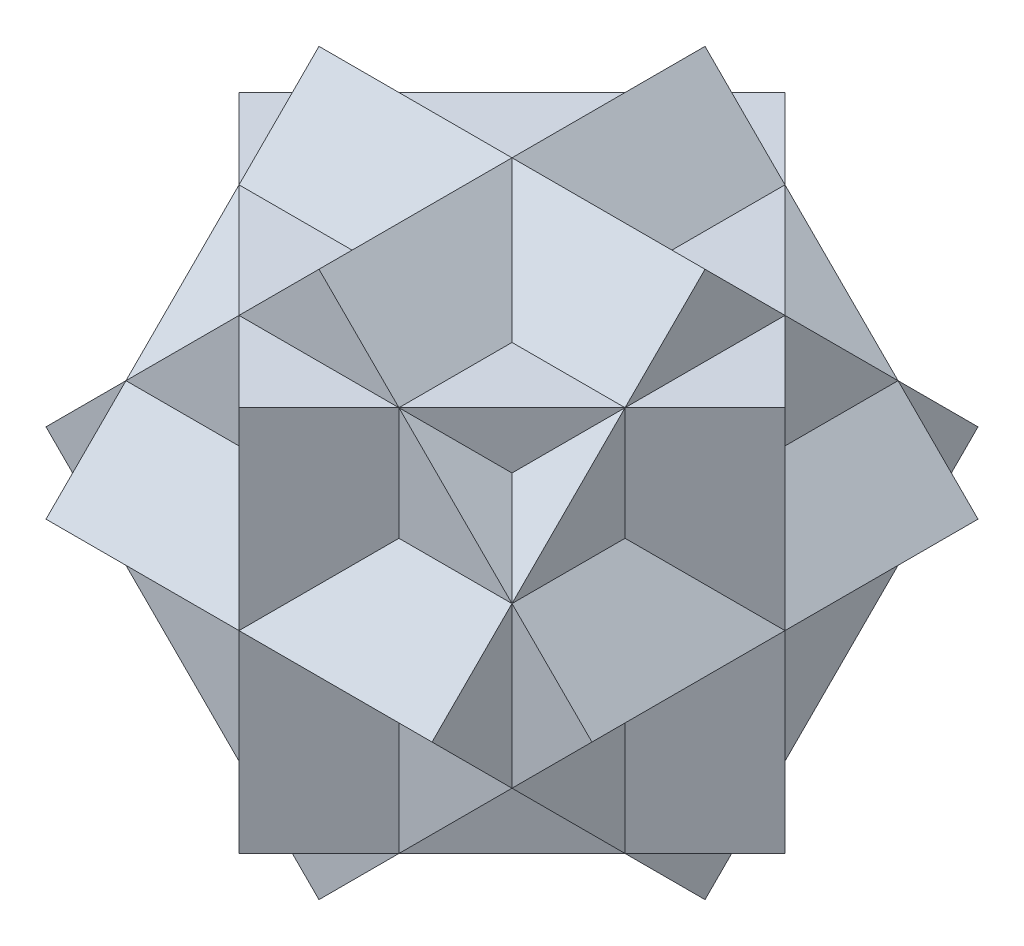
SolidWorks part; units mm, degrees
ref_plane "Front Plane" through (0, 0, 0) normal (0, 0, 1) x (1, 0, 0)
ref_plane "Top Plane" through (0, 0, 0) normal (0, 1, 0) x (1, 0, 0)
ref_plane "Right Plane" through (0, 0, 0) normal (1, 0, 0) x (0, 0, -1)
sketch "Sketch3" plane through (0, 0, 0) normal (0, 0, 1) x (1, 0, 0)
  line L0 (-160.803, 0) -> (0, 160.803)
  line L1 (-160.803, 0) -> (0, -160.803)
  line L2 (0, 160.803) -> (160.803, 0)
  line L3 (0, -160.803) -> (160.803, 0)
  line L4 (-160.803, 0) -> (160.803, 0) construction
  line L5 (0, 160.803) -> (0, -160.803) construction
  point P1 (0, 0)
  dimension "D1" = 227.4098
sketch "Sketch4" plane through (0, 0, 0) normal (0, 1, 0) x (1, 0, 0)
  line L0 (-160.803, 0) -> (0, 160.803)
  line L1 (-160.803, 0) -> (0, -160.803)
  line L2 (0, 160.803) -> (160.803, 0)
  line L3 (0, -160.803) -> (160.803, 0)
  line L4 (-160.803, 0) -> (160.803, 0) construction
  line L5 (0, 160.803) -> (0, -160.803) construction
  point P1 (0, 0)
sketch "Sketch5" plane through (0, 0, 0) normal (1, 0, 0) x (0, 0, -1)
  line L0 (-160.803, 0) -> (0, 160.803)
  line L1 (-160.803, 0) -> (0, -160.803)
  line L2 (0, 160.803) -> (160.803, 0)
  line L3 (0, -160.803) -> (160.803, 0)
  line L4 (-160.803, 0) -> (160.803, 0) construction
  line L5 (0, 160.803) -> (0, -160.803) construction
  line L6 (0, 160.803) -> (0, -160.803) construction
  point P1 (0, 0)
extrude "Boss-Extrude1" add sketch "Sketch3" along normal mid plane 227.4098
extrude "Boss-Extrude2" add sketch "Sketch4" along normal mid plane 227.4098
extrude "Boss-Extrude3" add sketch "Sketch5" along normal mid plane 227.4098
sketch "Sketch6" plane through (80.4015, -80.4015, 0) normal (0.7071, -0.7071, 0) x (0, 0, -1)
  line L16 (-4.9069, -111.1649) -> (-48.4129, -49.6381)
  line L17 (-48.4129, -49.6381) -> (-111.1649, -49.6381)
  line L18 (-111.1649, -49.6381) -> (-111.1649, -111.1649)
  line L19 (-111.1649, -111.1649) -> (-4.9069, -111.1649)
  line L20 (-4.9069, -111.1649) -> (-48.4129, -49.6381)
  line L21 (-48.4129, -49.6381) -> (-111.1649, -49.6381)
  line L22 (-111.1649, -49.6381) -> (-111.1649, -111.1649)
  line L23 (-111.1649, -111.1649) -> (-4.9069, -111.1649)
  dimension "D2" = 2.54
sketch "Sketch8" plane through (-80.4015, -80.4015, 0) normal (-0.7071, -0.7071, 0) x (0, 0, 1)
  line L8 (48.4129, -49.6381) -> (4.9069, -111.1649)
  line L9 (4.9069, -111.1649) -> (111.1649, -111.1649)
  line L10 (111.1649, -111.1649) -> (111.1649, -49.6381)
  line L11 (111.1649, -49.6381) -> (48.4129, -49.6381)
  line L12 (48.4129, -49.6381) -> (4.9069, -111.1649)
  line L13 (4.9069, -111.1649) -> (111.1649, -111.1649)
  line L14 (111.1649, -111.1649) -> (111.1649, -49.6381)
  line L15 (111.1649, -49.6381) -> (48.4129, -49.6381)
  dimension "D1" = 2.54
sketch "Sketch11" plane through (0, 0, 113.7049) normal (0, 0, 1) x (1, 0, 0)
  line L0 (0, -157.2109) -> (40.966, -116.2449)
  line L1 (40.966, -116.2449) -> (-40.966, -116.2449)
  line L2 (-40.966, -116.2449) -> (0, -157.2109)
  line L3 (0, -160.803) -> (47.0981, -113.7049)
  line L4 (47.0981, -113.7049) -> (-47.0981, -113.7049)
  line L5 (-47.0981, -113.7049) -> (0, -160.803)
  line L6 (0, -160.803) -> (47.0981, -113.7049) construction
  line L7 (47.0981, -113.7049) -> (-47.0981, -113.7049) construction
  line L8 (-47.0981, -113.7049) -> (0, -160.803) construction
  dimension "D2" = 2.54
sketch "Sketch12" plane through (0, -113.7049, 0) normal (0, -1, 0) x (1, 0, 0)
  line L0 (0, 157.2109) -> (-40.966, 116.2449)
  line L1 (-40.966, 116.2449) -> (40.966, 116.2449)
  line L2 (40.966, 116.2449) -> (0, 157.2109)
  line L3 (-47.0981, 113.7049) -> (47.0981, 113.7049)
  line L4 (47.0981, 113.7049) -> (0, 160.803)
  line L5 (0, 160.803) -> (-47.0981, 113.7049)
  line L6 (-47.0981, 113.7049) -> (47.0981, 113.7049) construction
  line L7 (47.0981, 113.7049) -> (0, 160.803) construction
  line L8 (0, 160.803) -> (-47.0981, 113.7049) construction
  dimension "D2" = 2.54
sketch "Sketch13" plane through (0, -80.4015, 80.4015) normal (0, -0.7071, 0.7071) x (1, 0, 0)
  line L0 (111.1649, -49.6381) -> (48.4129, -49.6381)
  line L1 (48.4129, -49.6381) -> (4.9069, -111.1649)
  line L2 (4.9069, -111.1649) -> (111.1649, -111.1649)
  line L3 (111.1649, -111.1649) -> (111.1649, -49.6381)
  line L4 (113.7049, -113.7049) -> (113.7049, -47.0981)
  line L5 (113.7049, -47.0981) -> (47.0981, -47.0981)
  line L6 (47.0981, -47.0981) -> (0, -113.7049)
  line L7 (0, -113.7049) -> (113.7049, -113.7049)
  line L8 (113.7049, -113.7049) -> (113.7049, -47.0981) construction
  line L9 (113.7049, -47.0981) -> (47.0981, -47.0981) construction
  line L10 (47.0981, -47.0981) -> (0, -113.7049) construction
  line L11 (0, -113.7049) -> (113.7049, -113.7049) construction
  dimension "D2" = 2.54
sketch "Sketch14" plane through (0, -113.7049, 0) normal (0, -1, 0) x (1, 0, 0)
  line L0 (49.6381, 107.5728) -> (49.6381, 49.6381)
  line L1 (49.6381, 49.6381) -> (107.5728, 49.6381)
  line L2 (107.5728, 49.6381) -> (49.6381, 107.5728)
  line L3 (47.0981, 47.0981) -> (113.7049, 47.0981)
  line L4 (113.7049, 47.0981) -> (47.0981, 113.7049)
  line L5 (47.0981, 113.7049) -> (47.0981, 47.0981)
  line L6 (47.0981, 47.0981) -> (113.7049, 47.0981) construction
  line L7 (113.7049, 47.0981) -> (47.0981, 113.7049) construction
  line L8 (47.0981, 113.7049) -> (47.0981, 47.0981) construction
  dimension "D2" = 2.54
sketch "Sketch15" plane through (80.4015, 0, 80.4015) normal (0.7071, 0, 0.7071) x (0.7071, 0, -0.7071)
  line L0 (39.1066, -111.1649) -> (0, -83.5123)
  line L1 (0, -83.5123) -> (-39.1066, -111.1649)
  line L2 (-39.1066, -111.1649) -> (39.1066, -111.1649)
  line L3 (47.0981, -113.7049) -> (0, -80.4015)
  line L4 (0, -80.4015) -> (-47.0981, -113.7049)
  line L5 (-47.0981, -113.7049) -> (47.0981, -113.7049)
  line L6 (47.0981, -113.7049) -> (0, -80.4015) construction
  line L7 (0, -80.4015) -> (-47.0981, -113.7049) construction
  line L8 (-47.0981, -113.7049) -> (47.0981, -113.7049) construction
  dimension "D2" = 2.54
sketch "Sketch16" plane through (80.4015, -80.4015, 0) normal (0.7071, -0.7071, 0) x (0, 0, -1)
  line L0 (-83.5123, 0) -> (-111.1649, 39.1066)
  line L1 (-111.1649, 39.1066) -> (-111.1649, -39.1066)
  line L2 (-111.1649, -39.1066) -> (-83.5123, 0)
  line L3 (-80.4015, 0) -> (-113.7049, 47.0981)
  line L4 (-113.7049, 47.0981) -> (-113.7049, -47.0981)
  line L5 (-113.7049, -47.0981) -> (-80.4015, 0)
  line L6 (-80.4015, 0) -> (-113.7049, 47.0981) construction
  line L7 (-113.7049, 47.0981) -> (-113.7049, -47.0981) construction
  line L8 (-113.7049, -47.0981) -> (-80.4015, 0) construction
  dimension "D2" = 2.54
sketch "Sketch17" plane through (80.4015, 0, 80.4015) normal (0.7071, 0, 0.7071) x (0.7071, 0, -0.7071)
  line L0 (-49.6381, -48.4129) -> (-111.1649, -4.9069)
  line L1 (-111.1649, -4.9069) -> (-111.1649, -111.1649)
  line L2 (-111.1649, -111.1649) -> (-49.6381, -111.1649)
  line L3 (-49.6381, -111.1649) -> (-49.6381, -48.4129)
  line L4 (-47.0981, -47.0981) -> (-113.7049, 0)
  line L5 (-113.7049, 0) -> (-113.7049, -113.7049)
  line L6 (-113.7049, -113.7049) -> (-47.0981, -113.7049)
  line L7 (-47.0981, -113.7049) -> (-47.0981, -47.0981)
  line L8 (-47.0981, -47.0981) -> (-113.7049, 0) construction
  line L9 (-113.7049, 0) -> (-113.7049, -113.7049) construction
  line L10 (-113.7049, -113.7049) -> (-47.0981, -113.7049) construction
  line L11 (-47.0981, -113.7049) -> (-47.0981, -47.0981) construction
  dimension "D2" = 2.54
sketch "Sketch19" plane through (0, 0, 113.7049) normal (0, 0, 1) x (1, 0, 0)
  line L0 (49.6381, -49.6381) -> (49.6381, -107.5728)
  line L1 (49.6381, -107.5728) -> (107.5728, -49.6381)
  line L2 (107.5728, -49.6381) -> (49.6381, -49.6381)
  line L3 (47.0981, -113.7049) -> (113.7049, -47.0981)
  line L4 (113.7049, -47.0981) -> (47.0981, -47.0981)
  line L5 (47.0981, -47.0981) -> (47.0981, -113.7049)
  line L6 (47.0981, -113.7049) -> (113.7049, -47.0981) construction
  line L7 (113.7049, -47.0981) -> (47.0981, -47.0981) construction
  line L8 (47.0981, -47.0981) -> (47.0981, -113.7049) construction
  dimension "D2" = 2.54
ref_axis "Axis1" through (0, -160.803, 113.7049) along (0, 0.8165, -0.5774)
ref_plane "Plane1" through (0, -160.803, 113.7049) normal (0, 0.8165, -0.5774) x (1, 0, 0)
ref_axis "Axis2" through (80.4015, -80.4015, 80.4015) along (-0.5774, 0.5774, -0.5774)
ref_plane "Plane2" through (80.4015, -80.4015, 80.4015) normal (-0.5774, 0.5774, -0.5774) x (0.8165, 0.4082, -0.4082)
ref_axis "Axis3" through (47.0981, -113.7049, 47.0981) along (-0.3574, 0.8629, -0.3574)
ref_plane "Plane3" through (47.0981, -113.7049, 47.0981) normal (-0.3574, 0.8629, -0.3574) x (0.9339, 0.3302, -0.1368)
ref_axis "Axis4" through (47.0981, -113.7049, 47.0981) along (-0.5774, -0.5774, -0.5774)
ref_plane "Plane4" through (0, -160.803, 0) normal (-0.5774, -0.5774, -0.5774) x (-0.8165, 0.4082, 0.4082)
equation "\"side_length\"= 4 * 2.238285"
equation "\"D1@Sketch3\"=\"side_length\""
equation "\"D1@Boss-Extrude1\"=\"side_length\""
equation "\"D1@Boss-Extrude2\"=\"side_length\""
equation "\"D1@Boss-Extrude3\"=\"side_length\""
equation "\"Joiner_spacing\"=0.1"
equation "\"D1@Sketch8\"=\"Joiner_spacing\""
equation "\"D2@Sketch11\"=\"Joiner_spacing\""
equation "\"D2@Sketch13\"=\"Joiner_spacing\""
equation "\"D2@Sketch14\"=\"Joiner_spacing\""
equation "\"D2@Sketch15\"=\"Joiner_spacing\""
equation "\"D2@Sketch16\"=\"Joiner_spacing\""
equation "\"D2@Sketch17\"=\"Joiner_spacing\""
equation "\"D2@Sketch19\"=\"Joiner_spacing\""
equation "\"D2@Sketch12\"=\"Joiner_spacing\""
